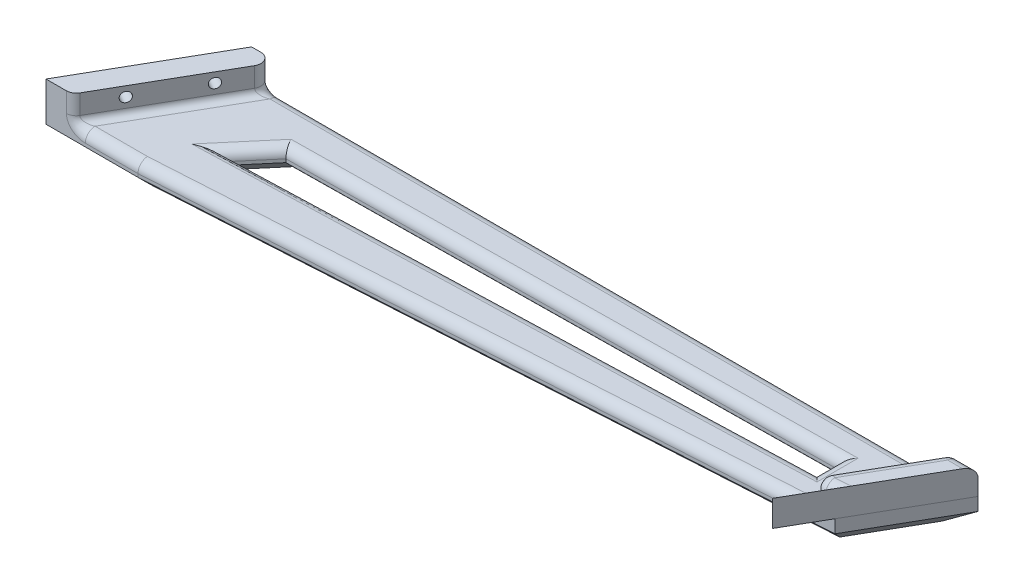
SolidWorks part; units mm, degrees
ref_plane "Front Plane" through (0, 0, 0) normal (0, 0, 1) x (1, 0, 0)
ref_plane "Top Plane" through (0, 0, 0) normal (0, 1, 0) x (1, 0, 0)
ref_plane "Right Plane" through (0, 0, 0) normal (1, 0, 0) x (0, 0, -1)
sketch "Sketch1" plane through (0, 0, 0) normal (0, 1, 0) x (1, 0, 0)
  line L1 (-100, 20) -> (150, 20)
  line L2 (-100, 20) -> (-100, -20)
  line L3 (-100, -20) -> (150, -20)
  line L4 (150, 20) -> (150, -20)
extrude "Boss-Extrude1" add sketch "Sketch1" along normal blind 8
sketch "Sketch2" plane through (0, 8, 0) normal (0, 1, 0) x (1, 0, 0)
  line L0 (-100, -24) -> (-72.4488, 24)
  line L1 (-72.4488, 24) -> (-100, 24)
  line L2 (-100, 24) -> (-100, -24)
  line L6 (150, 24) -> (150, -24)
  line L7 (150, -24) -> (122.4488, -24)
  line L8 (122.4488, -24) -> (150, 24)
extrude "Cut-Extrude1" cut sketch "Sketch2" against normal blind 8
sketch "Sketch3" plane through (0, 8, 0) normal (0, 1, 0) x (1, 0, 0)
  line L0 (-97.7041, -20) -> (-74.7447, 20)
  line L1 (-97.7041, -20) -> (-89.7041, -20)
  line L2 (-74.7447, 20) -> (-66.7147, 20)
  line L3 (-89.7041, -20) -> (-66.7147, 20)
  line L4 (116.7447, -20) -> (139.7041, 20)
  line L5 (124.7447, -20) -> (147.7341, 20)
  line L6 (139.7041, 20) -> (147.7341, 20)
  line L7 (116.7447, -20) -> (124.7447, -20)
extrude "Boss-Extrude2" add sketch "Sketch3" along normal blind 8
sketch "Sketch4" plane through (-58.7899, 0, -33.7886) normal (0.867, 0, 0.4983) x (0.4983, 0, -0.867)
  circle A0 centre (-30, 13) radius 1.5
  circle A1 centre (-50, 13) radius 1.5
extrude "Cut-Extrude5" cut sketch "Sketch4" against normal blind 8
sketch "Sketch5" plane through (0, 0, 0) normal (0, -1, 0) x (-1, 0, 0)
  line L0 (69.5305, -20) -> (-131.7364, -7.8191)
  line L1 (-131.7364, -7.8191) -> (-124.7447, -20)
  line L2 (-124.7447, -20) -> (69.5305, -20)
  line L3 (50.7947, 6.5663) -> (-116.2285, 8.7465)
  line L4 (-116.2285, 8.7465) -> (-116.2285, 2.0825)
  line L5 (-116.2285, 2.0825) -> (59.4953, -3.6959)
  line L7 (59.4953, -3.6959) -> (50.7947, 6.5663)
  point P5 (48.8934, -9.5795)
  point P8 (50.7947, -5.017)
  point P9 (40.7329, 8.7465)
  point P10 (44.3322, -8.8751)
  point P11 (50.7947, 6.5663)
  point P12 (59.4953, -3.6959)
extrude "Cut-Extrude6" cut sketch "Sketch5" against normal blind 30
fillet "Fillet1" radius 2 1 edges at (-78.2094, 8, 0) type face fillet first side face at (7.4407, 8, 1.6641) second side face at (-72.9914, 13, -9.0789)
fillet "Fillet2" radius 3 1 edges at (131.5763, 8, -5.8397) type face fillet first side face at (131.5763, 12, -5.8397) second side face at (8.3634, 8, 1.6641)
fillet "Chamfer1" radius 4 9 edges at (36.4797, 0, -20) (-86.2244, 0, 0) (-83.6173, 0, 20) (31.1029, 0, 13.9095) (139.7202, 0, -6.0905) (116.2285, 0, -5.4145) (28.3666, 0, 0.8067) (-55.145, 0, -1.4352) (32.7169, 0, -7.6564) profile chamfer
fillet "Fillet3" radius 3 1 edges at (131.5763, 16, -5.8397) type face fillet first side face at (133.4735, 16, -0.7721) second side face at (131.5763, 13.5, -5.8397)
fillet "Fillet4" radius 3 19 edges at (-89.7041, 13, 20) (-89.0284, 8.5858, 20) (145.4486, 16, -20) (140.7172, 15.1213, -20) (139.7041, 12, -20) (138.6909, 8.8787, -20) (-66.7147, 13, -20) (-66.0391, 8.5858, -20) (129.3842, 16, 7.9614) (124.4981, 15.1213, 8.2571) (123.4485, 12, 8.3206) (122.3989, 8.8787, 8.3842) (-78.4639, 8, 20) (35.9185, 8, -20) (25.1672, 8, 14.2688) (28.3666, 8, 0.8067) (116.2285, 8, -5.4145) (32.7169, 8, -7.6564) (-55.145, 8, -1.4352)
